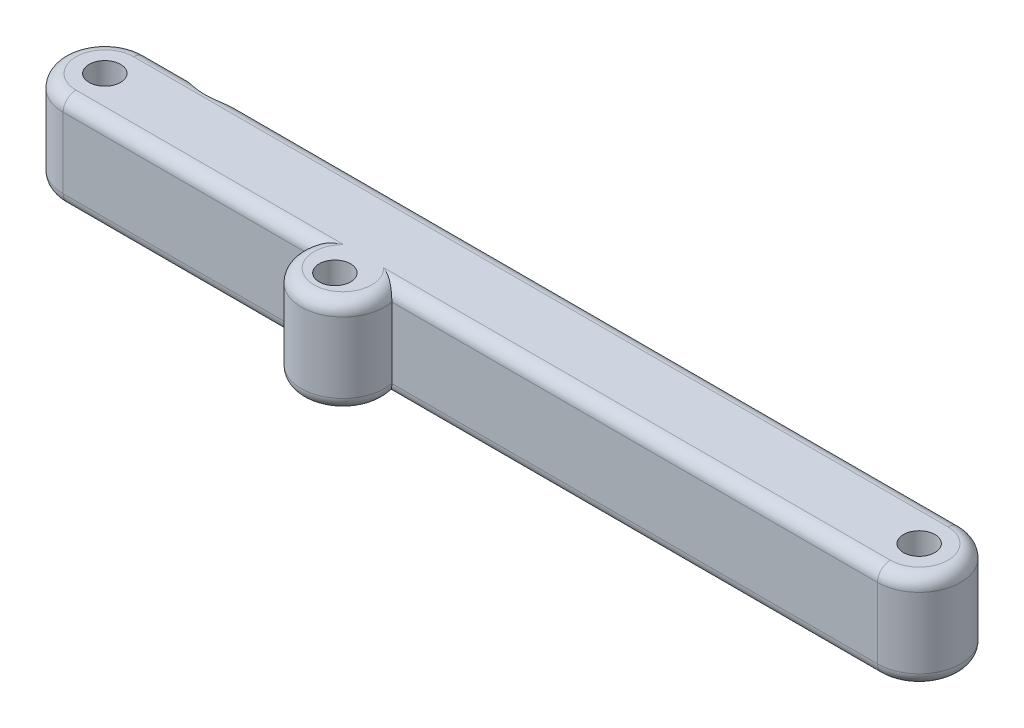
SolidWorks part; units mm, degrees
ref_plane "Front Plane" through (0, 0, 0) normal (0, 0, 1) x (1, 0, 0)
ref_plane "Top Plane" through (0, 0, 0) normal (0, 1, 0) x (1, 0, 0)
ref_plane "Right Plane" through (0, 0, 0) normal (1, 0, 0) x (0, 0, -1)
sketch "Sketch1" plane through (0, 0, 0) normal (0, 1, 0) x (1, 0, 0)
  line L0 (0, 0) -> (34315.2938, 0) construction
  line L1 (0, 0) -> (0, 34315.2938) construction
  line L2 (-80.645, -8.255) -> (80.645, -8.255)
  line L3 (-80.645, 8.255) -> (80.645, 8.255)
  arc A1 (-80.645, 8.255) -> (-80.645, -8.255) centre (-80.645, 0) ccw
  arc A2 (80.645, 8.255) -> (80.645, -8.255) centre (80.645, 0) cw
  circle A3 centre (-80.645, 0) radius 3.1115
  circle A4 centre (80.645, 0) radius 3.1115
  point P2 (-88.9, 0)
  point P7 (88.9, 0)
  point P13 (0, -8.255)
  point P16 (0, 8.255)
  dimension "D2" = 177.8
  dimension "D3" = 6.223
  dimension "D1" = 16.51
extrude "Boss-Extrude1" add sketch "Sketch1" along normal blind 19.05
sketch "Sketch2" plane through (0, 19.05, 0) normal (0, 1, 0) x (1, 0, 0)
  line L0 (0, 0) -> (50000, 0) construction
  line L1 (-23.6502, 0) -> (-23.6502, -8.255)
  line L2 (-80.645, -8.255) -> (80.645, -8.255)
  line L3 (80.645, 8.255) -> (-80.645, 8.255)
  line L4 (-80.645, -8.255) -> (80.645, -8.255)
  line L5 (80.645, 8.255) -> (-80.645, 8.255)
  line L6 (-23.6502, -18.0975) -> (49976.3498, -18.0975) construction
  circle A0 centre (-23.6502, -9.8425) radius 8.255
  circle A1 centre (-23.6502, -11.43) radius 3.1115
  arc A2 (-80.645, 8.255) -> (-80.645, -8.255) centre (-80.645, 0) ccw
  arc A3 (80.645, -8.255) -> (80.645, 8.255) centre (80.645, 0) ccw
  arc A4 (-80.645, 8.255) -> (-80.645, -8.255) centre (-80.645, 0) ccw
  arc A5 (80.645, -8.255) -> (80.645, 8.255) centre (80.645, 0) ccw
  point P16 (-23.6502, -18.0975)
  line M8 (-80.645, -8.255) -> (80.645, -8.255)
  dimension "D3" = 16.51
  dimension "D4" = 3.175
  dimension "D5" = 6.223
  dimension "D2" = 56.9948
  dimension "D6" = 1.5875
  dimension "D1" = 0
extrude "Boss-Extrude2" add sketch "Sketch2" along direction (0, 1, 0) on the side against the normal up to surface (19.05 mm away) contours L4 A0 L1 | L1 A0 M8 region at (-19.5998, 19.05, 8.4472) up to face at (0, 0, 0)
sketch "Sketch3" plane through (0, 19.05, 0) normal (0, 1, 0) x (1, 0, 0)
  line L0 (-67.183, -9.3167) -> (-67.183, 49990.6833) construction
  line L1 (-88.9, 0) -> (49911.1, 0) construction
  line L3 (-80.645, -8.255) -> (-31.7511, -8.255)
  line L15 (-80.645, -8.255) -> (-31.7511, -8.255)
  line L18 (-15.5493, -8.255) -> (80.645, -8.255)
  line L20 (-15.5493, -8.255) -> (80.645, -8.255)
  line L21 (80.645, 8.255) -> (-80.645, 8.255)
  line L22 (80.645, 8.255) -> (-80.645, 8.255)
  circle A0 centre (-67.183, -15.875) radius 9.525
  circle A1 centre (-67.183, 15.875) radius 9.525
  arc A3 (-80.645, 8.255) -> (-80.645, -8.255) centre (-80.645, 0) ccw
  arc A15 (-80.645, 8.255) -> (-80.645, -8.255) centre (-80.645, 0) ccw
  arc A18 (-31.7511, -8.255) -> (-15.5493, -8.255) centre (-23.6502, -9.8425) ccw
  arc A20 (-31.7511, -8.255) -> (-15.5493, -8.255) centre (-23.6502, -9.8425) ccw
  arc A21 (80.645, -8.255) -> (80.645, 8.255) centre (80.645, 0) ccw
  arc A22 (80.645, -8.255) -> (80.645, 8.255) centre (80.645, 0) ccw
  dimension "D2" = 13.462
  dimension "D3" = 19.05
  dimension "D4" = 7.62
  dimension "D1" = 0
extrude "Cut-Extrude1" cut sketch "Sketch3" against normal through all contours A1 L22 region at (-67.183, 19.05, -7.4861)
fillet "Fillet1" radius 2.54 14 edges at (32.5478, 0, 8.255) (88.9, 0, 0) (-56.1981, 0, 8.255) (-88.9, 0, 0) (32.5478, 19.05, 8.255) (88.9, 19.05, 0) (-56.1981, 19.05, 8.255) (-88.9, 19.05, 0) (-23.6502, 0, 18.0975) (-23.6502, 19.05, 18.0975) (9.5885, 0, -8.255) (-76.7715, 0, -8.255) (9.5885, 19.05, -8.255) (-76.7715, 19.05, -8.255)
